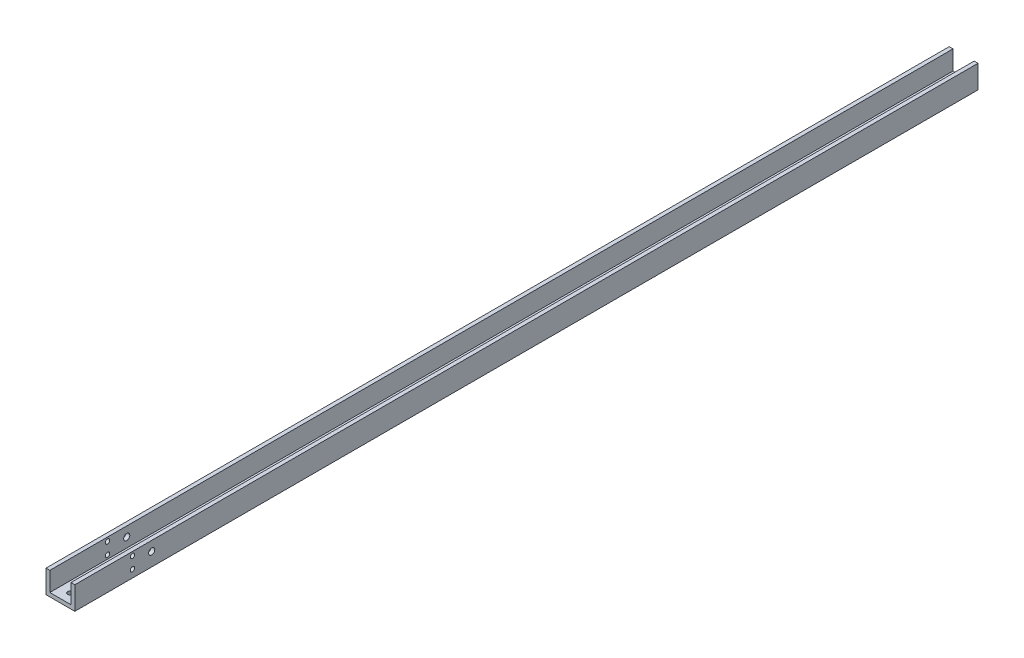
SolidWorks part; units mm, degrees
material "Alliage 1060"
ref_plane "Plan de face" through (0, 0, 0) normal (0, 0, 1) x (1, 0, 0)
ref_plane "Plan de dessus" through (0, 0, 0) normal (0, 1, 0) x (1, 0, 0)
ref_plane "Plan de droite" through (0, 0, 0) normal (1, 0, 0) x (0, 0, -1)
sketch "Esquisse1" plane through (0, 0, 0) normal (0, 0, 1) x (1, 0, 0)
  line L0 (-7.5, 0) -> (7.5, 0)
  line L1 (7.5, 0) -> (7.5, 12)
  line L2 (7.5, 12) -> (5.5, 12)
  line L3 (5.5, 12) -> (5.5, 2)
  line L4 (5.5, 2) -> (-5.5, 2)
  line L5 (0, 6.472) -> (0, -3.1073) construction
  line L6 (-5.5, 12) -> (-5.5, 2)
  line L7 (-7.5, 12) -> (-5.5, 12)
  line L8 (-7.5, 0) -> (-7.5, 12)
  point P10 (0, 2)
  point P13 (0, 0)
  dimension "D1" = 15
  dimension "D2" = 12
  dimension "D3" = 2
  dimension "D4" = 2
extrude "Boss.-Extru.1" add sketch "Esquisse1" along normal blind 470
sketch "Esquisse2" plane through (7.5, 0, 0) normal (1, 0, 0) x (0, 0, -1)
  line L0 (-440, 4) -> (-440, 13.011) construction
  line L1 (-470, 0) -> (-470, 12) construction
  line L2 (-470, 12) -> (0, 12) construction
  line L3 (-470, 2) -> (0, 2) construction
  circle A0 centre (-440, 10) radius 1.15
  circle A1 centre (-440, 4) radius 1.15
  circle A2 centre (-430, 7) radius 1.6
  dimension "D1" = 2.3
  dimension "D2" = 2.3
  dimension "D3" = 30
  dimension "D6" = 3.2
  dimension "D4" = 2
  dimension "D5" = 6
  dimension "D7" = 40
  dimension "D8" = 5
extrude "Enlèv. mat.-Extru.1" cut sketch "Esquisse2" against normal through all
hole_wizard "Trou pour taraudage pour trou taraudé M31" positions "Esquisse3" profile "Esquisse4" hole size "M3" standard "ISO" end condition through all
sketch "Esquisse3" plane through (0, 2, 0) normal (0, 1, 0) x (1, 0, 0)
  line L0 (5.5, -470) -> (-5.5, -470) construction
  line L2 (0, -545.3962) -> (0, -539.2293) construction
  point P2 (0, -465)
  dimension "D2" = 5
sketch "Esquisse4" plane through (0, 2, 465) normal (1, 0, 0) x (0, 0, 1)
  line L0 (0, 0) -> (0, 2)
  line L1 (0, 2) -> (1.25, 2)
  line L2 (1.25, 2) -> (1.25, 0)
  line L5 (1.25, 0) -> (0, 0)
  line L11 (0, -6.35) -> (0, 107.95) construction
  dimension "Diamètre du perçage jusqu'au prochain" = 2.5
  dimension "Profondeur du perçage jusqu'au prochain" = 2
sketch "Esquisse5" plane through (0, 2, 0) normal (0, 1, 0) x (1, 0, 0)
  line L0 (0, -467.2445) -> (0, -475.452) construction
  line L1 (5.5, -470) -> (5.5, 0) construction
  line L2 (-5.5, -470) -> (-5.5, 0) construction
  circle A0 centre (0, -467.2445) radius 1.25
  dimension "D1" = 2.5
extrude "Enlèv. mat.-Extru.2" [suppressed] cut sketch "Esquisse5" against normal through all
